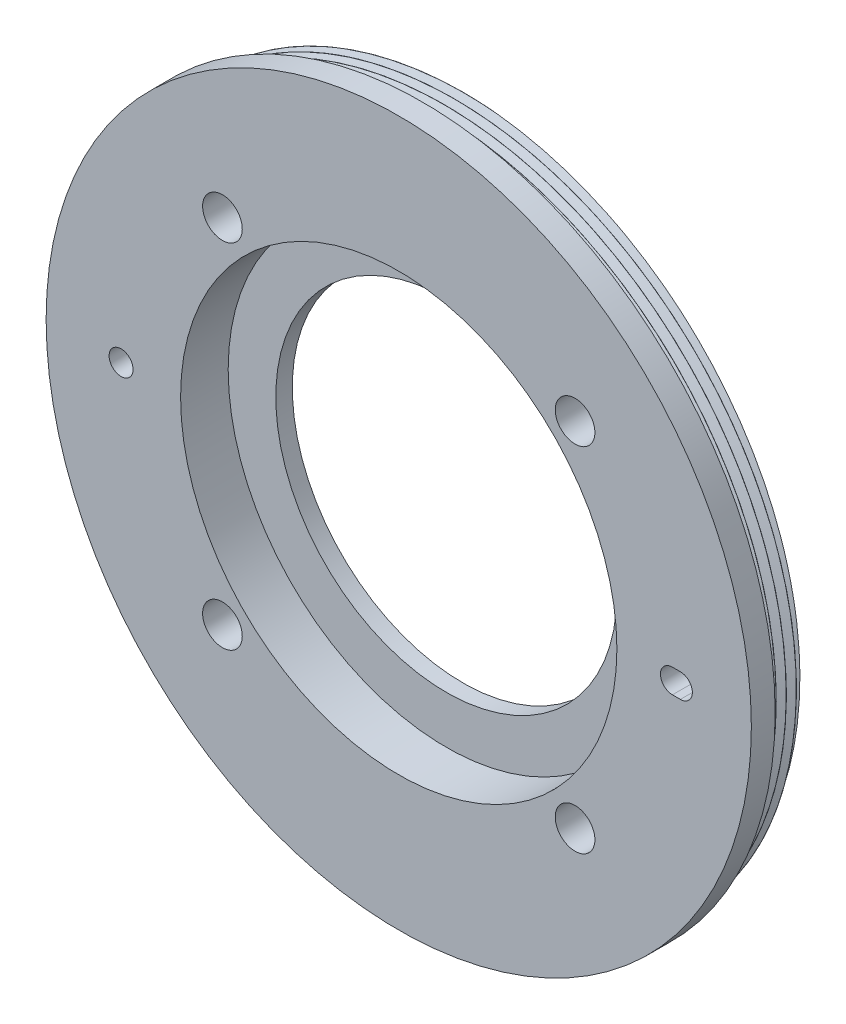
SolidWorks part; units mm, degrees
ref_plane "Front Plane" through (0, 0, 0) normal (0, 0, 1) x (1, 0, 0)
ref_plane "Top Plane" through (0, 0, 0) normal (0, 1, 0) x (1, 0, 0)
ref_plane "Right Plane" through (0, 0, 0) normal (1, 0, 0) x (0, 0, -1)
sketch "Sketch1" plane through (0, 0, 0) normal (0, 0, 1) x (1, 0, 0)
  circle A0 centre (0, 0) radius 43
  dimension "D1" = 86
extrude "Extrude1" add sketch "Sketch1" along normal blind 5.08
sketch "Sketch2" plane through (0, 0, 5.08) normal (0, 0, 1) x (1, 0, 0)
  circle A0 centre (0, 0) radius 44.45
  dimension "D1" = 88.9
extrude "Extrude2" add sketch "Sketch2" along normal blind 3
sketch "Sketch4" plane through (0, 0, 8.08) normal (0, 0, 1) x (1, 0, 0)
  line L0 (0, 0) -> (44.45, 0) construction
  circle A0 centre (0, 0) radius 44.45 construction
ref_plane "Plane1" through (44.45, 0, 8.08) normal (1, 0, 0) x (0, 0, -1)
sketch "Sketch5" plane through (0, 0, 8.08) normal (0, 0, 1) x (1, 0, 0)
  line L1 (22.225, -22.225) -> (-22.225, -22.225) construction
  line L2 (22.225, -22.225) -> (22.225, 22.225) construction
  line L3 (22.225, 22.225) -> (-22.225, 22.225) construction
  line L4 (-22.225, -22.225) -> (-22.225, 22.225) construction
  line L5 (22.225, -22.225) -> (-22.225, 22.225) construction
  line L6 (22.225, 22.225) -> (-22.225, -22.225) construction
  circle A0 centre (0, 0) radius 34.925 construction
  circle A1 centre (-22.225, 22.225) radius 2.5
  circle A2 centre (22.225, 22.225) radius 2.5
  circle A3 centre (22.225, -22.225) radius 2.5
  circle A4 centre (-22.225, -22.225) radius 2.5
  point P11 (0, 34.925)
  dimension "D2" = 69.85
  dimension "D3" = 5
  dimension "D1" = 44.45
extrude "Extrude4" cut sketch "Sketch5" against normal through all
sketch "Sketch10" plane through (0, 0, 0) normal (1, 0, 0) x (0, 0, -1)
  line L0 (-5.08, 43) -> (-4.455, 41.9175)
  line L1 (-5.08, -44.45) -> (-5.08, 44.45) construction
  line L2 (0, 43) -> (-5.08, 43) construction
  line L3 (-4.455, 41.9175) -> (-3.83, 43)
  line L4 (-3.83, 43) -> (-5.08, 43)
  line L5 (-4.455, 41.9175) -> (-4.455, 43) construction
  dimension "D1" = 60
  dimension "D2" = 1.25
ref_plane "Plane2" through (0, 0, 4.455) normal (0, 0, 1) x (1, 0, 0)
sketch "Sketch14" plane through (0, 0, 4.455) normal (0, 0, 1) x (1, 0, 0)
  circle A0 centre (0, 0) radius 41.9175
curve "Helix/Spiral1" pitch 1.27 height 5.08 radius 41.9175 centre (0, 0, 4.455) axis (0, 0, -1) start towards (0, 1, 0)
sweep "Cut-Sweep1" cut profiles "Sketch10" path "Helix/Spiral1"
sketch "Sketch15" plane through (0, 0, 0) normal (0, 0, -1) x (-1, 0, 0)
  line L0 (0, 0) -> (-34.5, 0) construction
  line L1 (0, 0) -> (35, 0) construction
  line L2 (-35.5, 1.51) -> (-34.5, 1.51)
  line L3 (-34.5, -1.51) -> (-35.5, -1.51)
  circle A0 centre (35, 0) radius 1.51
  arc A1 (-34.5, -1.51) -> (-34.5, 1.51) centre (-34.5, 0) ccw
  arc A2 (-35.5, 1.51) -> (-35.5, -1.51) centre (-35.5, 0) ccw
  dimension "D2" = 3.02
  dimension "D1" = 35
  dimension "D3" = 1
  dimension "D4" = 34.5
extrude "Extrude10" cut sketch "Sketch15" against normal blind 9.525
sketch "Sketch16" plane through (0, 0, 8.08) normal (0, 0, 1) x (1, 0, 0)
  circle A0 centre (0, 0) radius 27.5
  dimension "D1" = 55
extrude "Cut-Extrude1" cut sketch "Sketch16" against normal blind 6
sketch "Sketch17" plane through (0, 0, 2.08) normal (0, 0, 1) x (1, 0, 0)
  circle A0 centre (0, 0) radius 21.5
  dimension "D1" = 43
extrude "Cut-Extrude2" cut sketch "Sketch17" against normal up to surface (2.08 mm away) up to face at (35, 0, 0)
